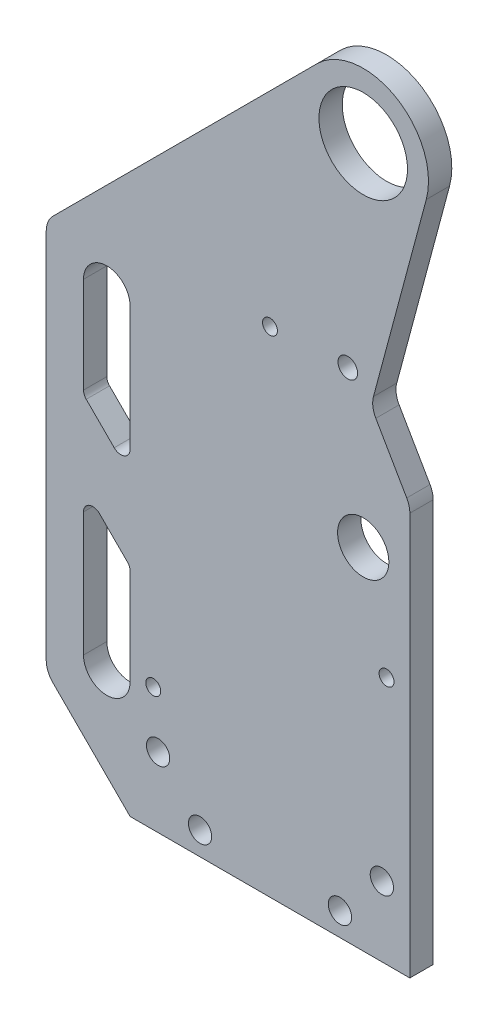
SolidWorks part; units mm, degrees
material "Thornel Mat VMA"
ref_plane "Front Plane" through (0, 0, 0) normal (0, 0, 1) x (1, 0, 0)
ref_plane "Top Plane" through (0, 0, 0) normal (0, 1, 0) x (1, 0, 0)
ref_plane "Right Plane" through (0, 0, 0) normal (1, 0, 0) x (0, 0, -1)
sketch "Sketch1" plane through (0, 0, 0) normal (0, 0, 1) x (1, 0, 0)
  line L0 (0, 103.759) -> (0, -103.759) construction
  line L1 (-30, 76) -> (50, 76)
  line L2 (-30, 76) -> (-30, 256)
  line L3 (-30, 256) -> (50, 256)
  line L4 (50, 76) -> (50, 256)
  circle A0 centre (20, 226) radius 9.5
  dimension "D1" = 150
  dimension "D5" = 19
  dimension "D2" = 20
  dimension "D3" = 180
  dimension "D4" = 80
extrude "Boss-Extrude1" add sketch "Sketch1" along normal blind 5
sketch "Sketch2" plane through (0, 0, 5) normal (0, 0, 1) x (1, 0, 0)
  line L0 (20, 226) -> (20, 151) construction
  line L1 (20, 226) -> (-17.1819, 226) construction
  circle A0 centre (20, 151) radius 5.5
  dimension "D3" = 11
  dimension "D1" = 75
  dimension "D2" = 90
extrude "Cut-Extrude1" cut sketch "Sketch2" against normal blind 30
sketch "Sketch3" plane through (0, 0, 5) normal (0, 0, 1) x (1, 0, 0)
  circle A0 centre (0, 182) radius 1.6
  circle A1 centre (25, 129.3013) radius 1.6
  circle A2 centre (-25.0329, 102.5335) radius 1.6
  circle A3 centre (-15, 81) radius 2.5
  circle A4 centre (15, 81) radius 2.5
  circle A5 centre (24, 91) radius 2.5
  circle A6 centre (-24, 91) radius 2.5
  dimension "D1" = 5
  dimension "D2" = 3.2
extrude "Cut-Extrude2" cut sketch "Sketch3" against normal blind 5
sketch "Sketch4" plane through (0, 0, 5) normal (0, 0, 1) x (1, 0, 0)
  line L0 (10.1005, 235.8995) -> (-46.7482, 179.0508)
  line L1 (-46.7482, 179.0508) -> (-46.7482, 110.6012)
  line L2 (-46.7482, 110.6012) -> (-30, 76)
  line L3 (33.523, 222.3765) -> (21.6639, 178.118)
  line L4 (21.6639, 178.118) -> (30, 163.6795)
  line L5 (30, 163.6795) -> (30, 76)
  line L6 (-30, 76) -> (50, 76) construction
  line L7 (30, 76) -> (50, 76)
  line L8 (50, 76) -> (50, 256)
  line L9 (50, 256) -> (-30, 256)
  line L10 (-30, 256) -> (-68.6435, 166)
  line L11 (-68.6435, 166) -> (-57.2516, 84.4416)
  line L12 (-57.2516, 84.4416) -> (-30, 76)
  circle A0 centre (20, 226) radius 14
  circle A1 centre (20, 151) radius 5.5 construction
  point P22 (0, 0)
  point P23 (10.0073, 235.8054)
  line M14 (-30, 256) -> (-30, 76)
  line M15 (-30, 76) -> (50, 76)
  line M16 (50, 76) -> (50, 256)
  line M17 (50, 256) -> (-30, 256)
  dimension "D1" = 28
  dimension "D4" = 15
  dimension "D5" = 60
  dimension "D2" = 75
  dimension "D3" = 45
  dimension "D6" = 60
extrude "Cut-Extrude3" cut sketch "Sketch4" against normal blind 10 contours A0 L3 L4 L5 L0 M15 M16 M17 M14 region at (-11.3426, 217.2421, 5)
sketch "Sketch5" plane through (0, 0, 5) normal (0, 0, 1) x (1, 0, 0)
  line L0 (-30, 195.799) -> (-46.5355, 179.2635)
  line L1 (-48, 175.7279) -> (-48, 96.0711)
  line L2 (-46.5355, 92.5355) -> (-30, 76)
  line L4 (10.1005, 235.8995) -> (-30, 195.799) construction
  line L6 (-30, 195.799) -> (-30, 76) construction
  line L15 (-30, 76) -> (30, 76) construction
  line L16 (-35, 170.799) -> (-35, 101) construction
  line L17 (-30, 170.799) -> (-30, 101)
  line L18 (-40, 170.799) -> (-40, 101)
  line L19 (-30, 139.3848) -> (-30, 122.4142)
  line L20 (-30, 139.3848) -> (-40, 149.3848)
  line L21 (-30, 122.4142) -> (-40, 132.4142)
  line L22 (-40, 149.3848) -> (-40, 132.4142)
  line L23 (-40, 149.3848) -> (-30, 122.4142)
  arc A0 (-30, 170.799) -> (-40, 170.799) centre (-35, 170.799) ccw
  arc A1 (-40, 101) -> (-30, 101) centre (-35, 101) ccw
  arc A2 (-48, 96.0711) -> (-46.5355, 92.5355) centre (-43, 96.0711) ccw
  arc A3 (-46.5355, 179.2635) -> (-48, 175.7279) centre (-43, 175.7279) ccw
  point P14 (-35, 135.8995)
  point P19 (0, 0)
  point P26 (-48, 94)
  point P29 (-48, 177.799)
  line M19 (-30, 195.799) -> (-30, 76)
  dimension "D6" = 5
  dimension "D9" = 5
  dimension "D1" = 18
  dimension "D2" = 45
  dimension "D3" = 7
  dimension "D4" = 7
  dimension "D5" = 8
  dimension "D7" = 12
  dimension "D8" = 135
extrude "Boss-Extrude2" add sketch "Sketch5" against normal blind 5 contours L1 L2 L0 A1 L18 A0 L17 M19 | L16 L23 L18 L21 | L20 L16 L23 L17 | L16 L20 L23 | L23 L16 L21 region at (-41.0144, 135.8995, 5) region at (-32.2222, 135.0073, 5) region at (-33.3333, 128.576, 5) region at (-36.6667, 143.223, 5) region at (-37.7778, 136.7917, 5)
fillet "Fillet1" radius 2 4 edges at (-40, 132.4142, 2.5) (-40, 149.3848, 2.5) (-30, 122.4142, 2.5) (-30, 139.3848, 2.5)
fillet "Fillet2" radius 5 2 edges at (30, 163.6795, 2.5) (21.6639, 178.118, 2.5)
sketch "Sketch6" plane through (0, 0, 5) normal (0, 0, 1) x (1, 0, 0)
  line L0 (33.523, 222.3765) -> (22.2, 180.1185) construction
  line L1 (22.6995, 176.3244) -> (29.3301, 164.8397) construction
  circle A0 centre (16.6892, 182.7344) radius 2.1
  dimension "D1" = 4.2
  dimension "D2" = 6
  dimension "D3" = 2
extrude "Cut-Extrude4" cut sketch "Sketch6" against normal blind 5
